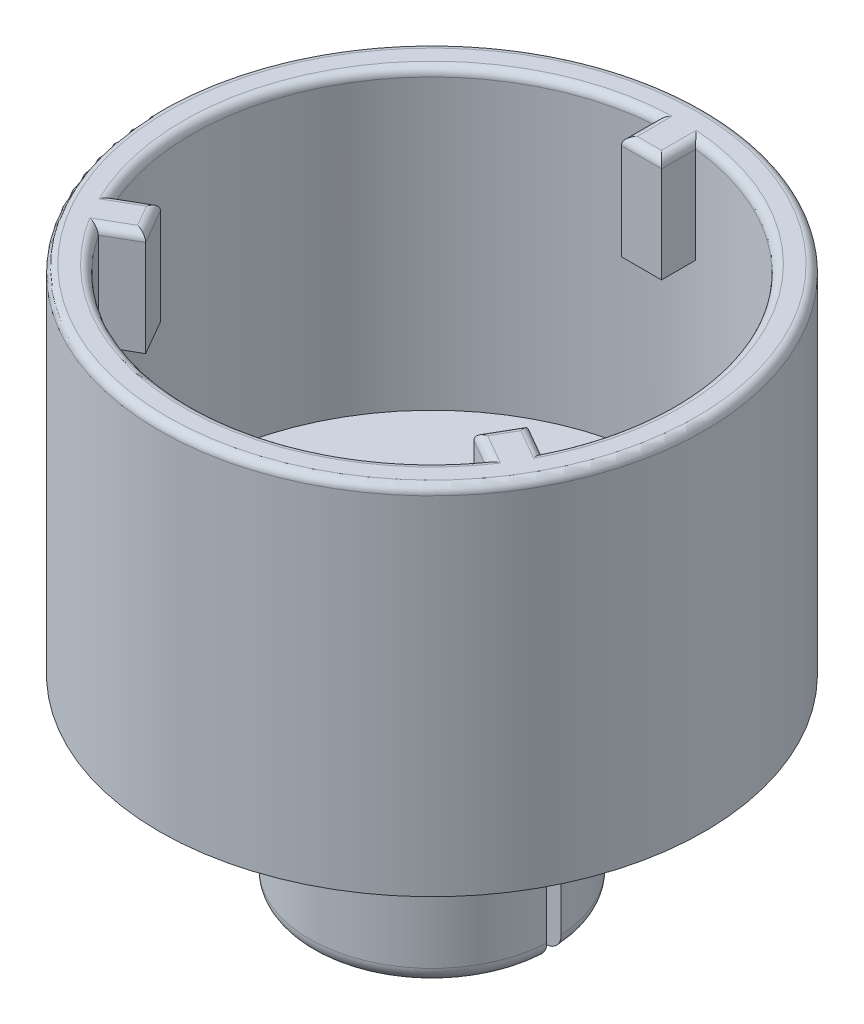
SolidWorks part; units mm, degrees
ref_plane "Front Plane" through (0, 0, 0) normal (0, 0, 1) x (1, 0, 0)
ref_plane "Top Plane" through (0, 0, 0) normal (0, 1, 0) x (1, 0, 0)
ref_plane "Right Plane" through (0, 0, 0) normal (1, 0, 0) x (0, 0, -1)
sketch "Sketch1" plane through (0, 0, 0) normal (0, 1, 0) x (1, 0, 0)
  circle A0 centre (0, 0) radius 34
  dimension "D1" = 68
extrude "Boss-Extrude1" add sketch "Sketch1" along normal blind 44.3
sketch "Sketch2" plane through (0, 44.3, 0) normal (0, 1, 0) x (1, 0, 0)
  circle A0 centre (0, 0) radius 30
  dimension "D1" = 60
extrude "Cut-Extrude1" cut sketch "Sketch2" against normal blind 37
sketch "Sketch3" plane through (0, 0, 0) normal (0, -1, 0) x (1, 0, 0)
  circle A0 centre (0, 0) radius 19.5
  dimension "D1" = 39
extrude "Boss-Extrude2" add sketch "Sketch3" along normal blind 7
sketch "Sketch4" plane through (0, -7, 0) normal (0, -1, 0) x (1, 0, 0)
  circle A0 centre (0, 0) radius 15.25
  dimension "D1" = 30.5
extrude "Boss-Extrude3" add sketch "Sketch4" along normal blind 16
fillet "Fillet1" radius 5 1 edges at (0, 0, -19.5)
sketch "Sketch5" plane through (0, 44.3, 0) normal (0, 1, 0) x (1, 0, 0)
  line L0 (-1.9905, 29.9339) -> (-1.9905, 25.6053)
  line L1 (-1.9905, 25.6053) -> (3.0302, 25.6053)
  line L2 (3.0302, 25.6053) -> (3.0302, 29.8466)
  line L3 (26.9188, -13.2431) -> (23.1701, -11.0788)
  line L4 (23.1701, -11.0788) -> (20.6597, -15.4269)
  line L5 (20.6597, -15.4269) -> (24.3328, -17.5475)
  line L6 (-24.9282, -16.6908) -> (-21.1796, -14.5265)
  line L7 (-21.1796, -14.5265) -> (-23.69, -10.1784)
  line L8 (-23.69, -10.1784) -> (-27.363, -12.299)
  circle A0 centre (0, 0) radius 30 construction
  arc A1 (24.3328, -17.5475) -> (26.9188, -13.2431) centre (0, 0) ccw
  circle A2 centre (0, 0) radius 30
  arc A3 (3.0302, 29.8466) -> (-1.9905, 29.9339) centre (0, 0) ccw
  arc A4 (-27.363, -12.299) -> (-24.9282, -16.6908) centre (0, 0) ccw
  point P19 (0, 0)
  dimension "D1" = 0
  dimension "D2" = 3
extrude "Boss-Extrude4" add sketch "Sketch5" against normal blind 13
sketch "Sketch7" plane through (0, -23, 0) normal (0, -1, 0) x (1, 0, 0)
  line L1 (33.0968, 0.9034) -> (-33.0968, 0.9034)
  line L2 (33.0968, 0.9034) -> (33.0968, -0.9034)
  line L3 (33.0968, -0.9034) -> (-33.0968, -0.9034)
  line L4 (-33.0968, 0.9034) -> (-33.0968, -0.9034)
  line L5 (33.0968, 0.9034) -> (-33.0968, -0.9034) construction
  line L6 (33.0968, -0.9034) -> (-33.0968, 0.9034) construction
  point P0 (0, 0)
extrude "Cut-Extrude2" cut sketch "Sketch7" against normal up to surface (16 mm away) up to face at (0, -7, -15.25)
fillet "Fillet2" radius 2 2 edges at (0, -23, 15.25) (0, -23, -15.25)
sketch "Sketch8" plane through (0, 7.3, 0) normal (0, 1, 0) x (1, 0, 0)
  circle A0 centre (0, 0) radius 10.3601
fillet "Fillet3" radius 1 4 edges at (26.2377, 44.3, -14.5459) (-25.716, 44.3, -15.4495) (-0.5217, 44.3, 29.9955) (0, 44.3, 34)
fillet "Fillet4" radius 1 9 edges at (-23.4879, 44.3, 15.8592) (-22.4348, 44.3, 12.3525) (-25.9617, 44.3, 11.49) (3.0302, 44.3, -28.2284) (-1.9905, 44.3, -28.2707) (0.5198, 44.3, -25.6053) (25.4784, 44.3, 12.4115) (21.9149, 44.3, 13.2529) (22.9314, 44.3, 16.7385)
sketch "Sketch9" plane through (0, 7.3, 0) normal (0, 1, 0) x (1, 0, 0)
  circle A0 centre (0, 0) radius 7.5
  dimension "D1" = 15
extrude "Cut-Extrude3" cut sketch "Sketch9" against normal through all
